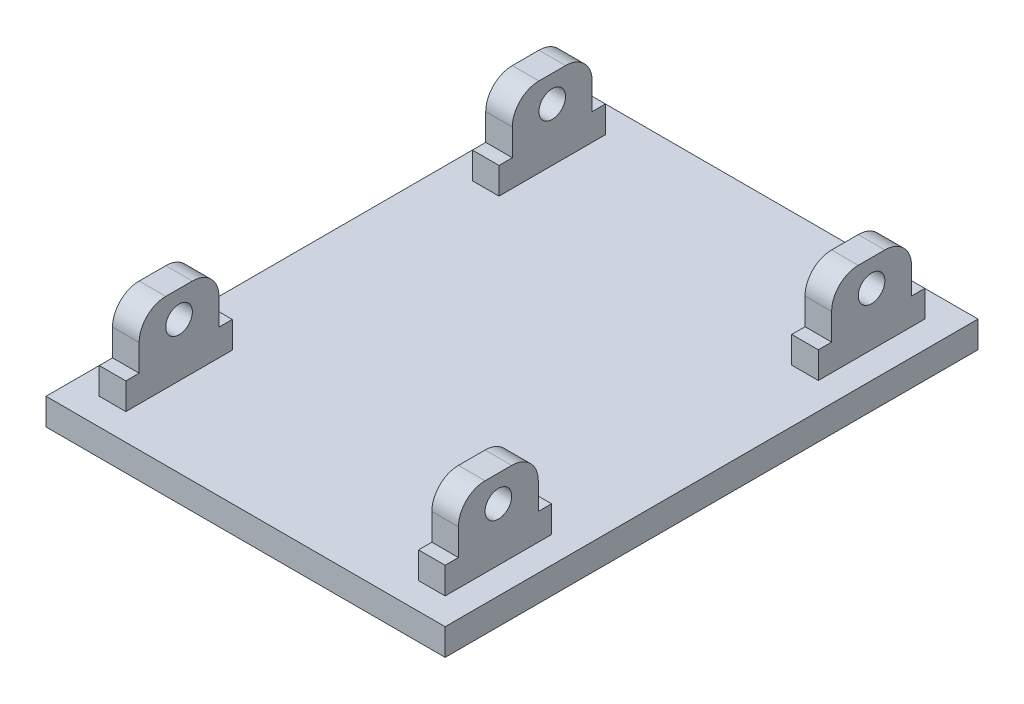
SolidWorks part; units mm, degrees
material "炭素鋼(普通)"
ref_plane "VERT" through (0, 0, 0) normal (0, 0, 1) x (1, 0, 0)
ref_plane "HOR" through (0, 0, 0) normal (0, 1, 0) x (1, 0, 0)
ref_plane "CTR" through (0, 0, 0) normal (1, 0, 0) x (0, 0, -1)
ref_axis "A_X" through (82.5, 0, 0) along (-1, 0, 0)
ref_axis "A_Y" through (0, 42, 0) along (0, -1, 0)
ref_axis "A_Z" through (0, 0, 110.1345) along (0, 0, -1)
sketch3d "PNT_CG"
  point P0 (0, 0, 0)
sketch "Sketch1" plane through (0, 0, 0) normal (0, 1, 0) x (1, 0, 0)
  line L0 (0, -55) -> (0, 55) construction
  line L1 (-75, 100.1223) -> (75, 100.1223)
  line L2 (-75, 100.1223) -> (-75, -100.1223)
  line L3 (-75, -100.1223) -> (75, -100.1223)
  line L4 (75, 100.1223) -> (75, -100.1223)
  line L5 (-55, 0) -> (55, 0) construction
  point P4 (0, 100.1223)
  point P7 (75, 0)
  dimension "D1" = 200.2446
  dimension "D2" = 150
extrude "Boss-Extrude1" add sketch "Sketch1" along normal blind 10
sketch "Sketch2" plane through (0, 10, 0) normal (0, 1, 0) x (1, 0, 0)
  line L0 (75, -100.1223) -> (75, 100.1223) construction
  line L1 (65, -90.1223) -> (55, -90.1223)
  line L2 (65, -90.1223) -> (65, -50.1223)
  line L3 (65, -50.1223) -> (55, -50.1223)
  line L4 (55, -90.1223) -> (55, -50.1223)
  line L5 (-75, -100.1223) -> (75, -100.1223) construction
  dimension "D1" = 40
  dimension "D2" = 10
  dimension "D3" = 10
  dimension "D4" = 10
extrude "Boss-Extrude2" add sketch "Sketch2" along normal blind 10 separate body
sketch "Sketch4" plane through (65, 0, 0) normal (1, 0, 0) x (0, 0, -1)
  line L0 (-90.1223, 20) -> (-50.1223, 20) construction
  line L1 (-85.1223, 20) -> (-55.1223, 20)
  line L2 (-85.1223, 20) -> (-85.1223, 40)
  line L3 (-85.1223, 40) -> (-55.1223, 40)
  line L4 (-55.1223, 20) -> (-55.1223, 40)
  point P6 (-70.1223, 20)
  point P7 (-70.1223, 40)
  dimension "D1" = 20
  dimension "D2" = 30
extrude "Boss-Extrude3" add sketch "Sketch4" against normal blind 10 separate body
sketch "Sketch5" plane through (65, 0, 0) normal (1, 0, 0) x (0, 0, -1)
  line L0 (-55.1223, 40) -> (-85.1223, 40) construction
  circle A0 centre (-70.1223, 30) radius 5
  point P2 (0, 0)
  point P5 (-70.1223, 40)
  dimension "D1" = 10
  dimension "D2" = 10
fillet "Fillet1" radius 10 2 edges at (60, 40, 55.1223) (60, 40, 85.1223)
extrude "Cut-Extrude2" cut sketch "Sketch5" against normal blind 10 contours A0
combine bodies "Combine1" operation type add bodies to combine 106 102
mirror "Mirror1" about plane through (0, 0, 0) normal (0, 0, 1) of bodies 107
mirror "Mirror3" about plane through (0, 0, 0) normal (1, 0, 0) of bodies 108 107
